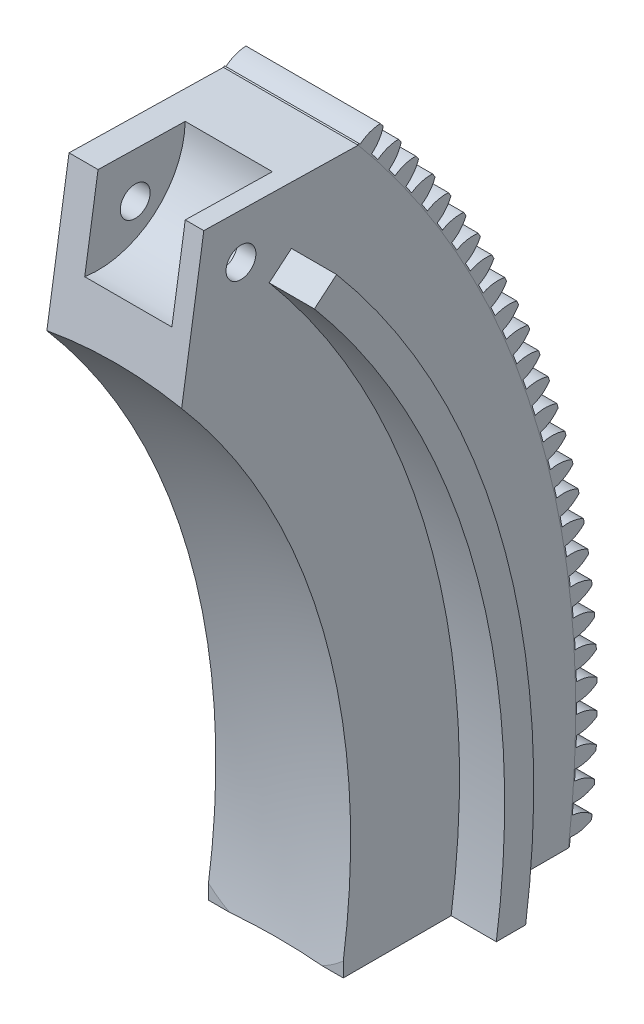
SolidWorks part; units mm, degrees
material "ABS"
ref_plane "Front Plane" through (0, 0, 0) normal (0, 0, 1) x (1, 0, 0)
ref_plane "Top Plane" through (0, 0, 0) normal (0, 1, 0) x (1, 0, 0)
ref_plane "Right Plane" through (0, 0, 0) normal (1, 0, 0) x (0, 0, -1)
ref_plane "Plane2" through (6.35, 0, 0) normal (1, 0, 0) x (0, 0, -1)
sketch "Sketch1" plane through (0, 0, 0) normal (1, 0, 0) x (0, 0, -1)
  line L0 (-1000, 0) -> (152.4, 0) construction
  line L1 (152.4, 0) -> (152.4, -25.4)
  line L2 (0, 0) -> (116.7452, 97.9608) construction
  line L4 (203.2, 0) -> (49000, 0) construction
  line L7 (152.4, -25.4) -> (203.2, -25.4) construction
  line L8 (203.2, 0) -> (203.2, -25.4) construction
  line L10 (-19.9245, -15.6845) -> (159.6649, 125.6875) construction
  line L61 (160.8976, 124.1056) -> (0, 0) construction
  line L62 (136.2027, 114.2876) -> (121.9167, 131.313) construction
  line L63 (116.7452, 97.9608) -> (121.9167, 131.313)
  line L64 (152.4, -25.4) -> (201.6062, -25.4)
  line L67 (121.9167, 131.313) -> (155.6602, 130.6144)
  line L68 (0, 0) -> (35966.99, 34732.9185) construction
  line L69 (159.6736, 125.6943) -> (159.6985, 125.714) construction
  arc A2 (152.4, 0) -> (116.7452, 97.9608) centre (0, 0) ccw
  circle A19 centre (0, 0) radius 203.2 construction
  arc A22 (155.6602, 130.6144) -> (203.2, 0) centre (0, 0) cw
  arc A23 (203.2, 0) -> (201.6062, -25.4) centre (0, 0) cw
  point P6 (159.6985, 125.714)
  point P7 (116.7452, 97.9608)
  dimension "D1" = 152.4
  dimension "D2" = 6.35
  dimension "D12" = 406.4
  dimension "D3" = 40
  dimension "D4" = 50.8
  dimension "D5" = 25.4
  dimension "D11" = 22.225
  dimension "D13" = 44
sketch "Sketch2" plane through (6.35, 0, 0) normal (1, 0, 0) x (0, 0, -1)
  line L0 (0, 0) -> (165.1, 0) construction
  line L1 (165.1, 0) -> (190.5, 0) construction
  line L2 (0, 0) -> (49240.3877, 8682.4089) construction
  circle A0 centre (165.1, 0) radius 3.2639
  circle A1 centre (190.5, 0) radius 3.2639
  arc A3 (165.1, 0) -> (162.5918, 28.6693) centre (0, 0) ccw construction
  circle A4 centre (162.5918, 28.6693) radius 3.2639
  arc A5 (190.5, 0) -> (187.6059, 33.08) centre (0, 0) ccw construction
  circle A6 centre (187.6059, 33.08) radius 3.2639
  dimension "D3" = 6.5278
  dimension "D4" = 6.5278
  dimension "D6" = 6.5278
  dimension "D7" = 6.5278
  dimension "D1" = 165.1
  dimension "D2" = 25.4
  dimension "D5" = 10
sketch "Sketch11" plane through (6.35, 0, 0) normal (1, 0, 0) x (0, 0, -1)
  line L0 (-785.502, -659.1144) -> (0, 0) construction
  line L2 (-1000, 0) -> (0, 0) construction
  line L4 (155.6602, 130.6144) -> (159.3372, 133.6998)
  line L5 (159.3372, 133.6998) -> (921.7047, 773.4021) construction
  line L6 (208, 0) -> (208, -25.4) construction
  line L7 (208, -25.4) -> (198.9391, -25.4) construction
  line L8 (201.6062, -25.4) -> (206.4433, -25.4)
  line L9 (203.2, 0) -> (208, 0) construction
  arc A0 (-230, 0) -> (-176.1902, -147.8412) centre (0, 0) ccw construction
  arc A1 (-208, 0) -> (-159.3372, -133.6998) centre (0, 0) ccw construction
  arc A2 (-205.6, 0) -> (-157.4987, -132.1571) centre (0, 0) ccw construction
  arc A3 (208, 0) -> (159.3372, 133.6998) centre (0, 0) ccw
  arc A4 (230, 0) -> (176.1902, 147.8412) centre (0, 0) ccw construction
  arc A5 (-205.6, 0) -> (-157.4987, -132.1571) centre (0, 0) ccw
  arc A6 (155.6602, 130.6144) -> (203.2, 0) centre (0, 0) cw
  arc A7 (208, 0) -> (206.4433, -25.4) centre (0, 0) cw
  arc A8 (203.2, 0) -> (201.6062, -25.4) centre (0, 0) cw
  dimension "D1" = 460
  dimension "D2" = 416
  dimension "D4" = 203.2
  dimension "D3" = 2.4
  dimension "D6" = 25.4
extrude "Boss-Extrude2" add sketch "Sketch11" against normal blind 6.35 contours A3 L4 region at (6.35, 130.8741, -158.5753)
sketch "Sketch12" plane through (6.35, 0, 0) normal (1, 0, 0) x (0, 0, -1)
  line L0 (0, 0) -> (208, 0) construction
  line L2 (205.994, 1.5708) -> (205.994, -1.5708) construction
  line L3 (0, 0) -> (203.4969, 1.1234) construction
  line L4 (201.6783, 0) -> (208.9831, 2.6587) construction
  line L5 (0, 0) -> (208.9757, 3.1872) construction
  line L6 (205.994, 1.5708) -> (205.9461, 4.712) construction
  circle A0 centre (0, 0) radius 206 construction
  arc A1 (206.4433, -25.4) -> (159.3372, 133.6998) centre (0, 0) ccw construction
  circle A2 centre (0, 0) radius 203.5 construction
  arc A3 (203.4969, 1.1234) -> (208.9694, 3.5771) centre (203.4559, 8.5441) ccw
  arc A4 (207.4358, -25.5221) -> (208.9694, -3.5771) centre (0, 0) cw construction
  arc A5 (203.4969, -1.1234) -> (208.9694, -3.5771) centre (203.4559, -8.5441) cw
  arc A6 (207.4358, -25.5221) -> (160.1033, 134.3426) centre (0, 0) ccw
  arc A7 (207.4358, -25.5221) -> (208.9694, 3.5771) centre (0, 0) ccw construction
  arc A8 (203.4969, 1.1234) -> (203.4969, -1.1234) centre (0, 0) cw
  arc A9 (206.4433, -25.4) -> (159.3372, 133.6998) centre (0, 0) ccw construction
  arc A10 (208.9694, 3.5771) -> (208.9694, -3.5771) centre (0, 0) cw
  point P9 (208.9694, -3.118)
  point P23 (208.9694, -3.525)
  dimension "D1" = 412
  dimension "D3" = 20
  dimension "D4" = 0.874
  dimension "D5" = 4.5
  dimension "D2" = 1
extrude "Boss-Extrude3" add sketch "Sketch1" along normal blind 29.464
extrude "Cut-Extrude4" cut sketch "Sketch12" against normal blind 6.35
pattern_circular "CirPattern3" count 206 every 1.748 about axis through (0, 0, 0) along (1, 0, 0) of "Cut-Extrude4"
sketch "Sketch15" plane through (6.35, 0, 0) normal (1, 0, 0) x (0, 0, -1)
  line L0 (0, 0) -> (130.0347, 121.2593) construction
  line L1 (-196961.5506, -34729.6355) -> (246201.9383, 43412.0444) construction
  circle A0 centre (130.0347, 121.2593) radius 3.2639
  dimension "D3" = 6.5278
  dimension "D1" = 177.8
  dimension "D2" = 33
extrude "Cut-Extrude7" cut sketch "Sketch15" against normal through all both and the other way through all
sketch "Sketch21" plane through (0, 0, 0) normal (0, 1, 0) x (1, 0, 0)
  line L0 (0, 0) -> (-11.1125, 0) construction
  line L1 (12.7, 0) -> (12.7, 152.4) construction
  line L2 (0, 0) -> (12.7, 0) construction
  line L3 (-11.1125, 0) -> (-11.1125, 38.1) construction
  line L4 (-11.1125, 38.1) -> (-127.8666, 38.1) construction
  line L5 (-11.1125, 38.1) -> (105.6416, 38.1) construction
  line L6 (107.5153, 38.1) -> (-49892.4847, 38.1) construction
  line L7 (-1000, 0) -> (49000, 0) construction
  line L8 (14.732, 38.1) -> (14.732, 152.4) construction
  line L9 (29.464, 152.4) -> (0, 152.4) construction
  line L10 (-76.1776, 38.1) -> (157.3306, 38.1) construction
  line L11 (29.464, 152.4) -> (0, 152.4) construction
  line L12 (0, 152.4) -> (14.732, 152.4) construction
  line L13 (14.732, 152.4) -> (14.732, 130.0627) construction
  line L15 (-76.1776, 38.1) -> (-102.108, 38.1)
  line L16 (105.6416, 38.1) -> (131.572, 38.1)
  line L17 (-76.1776, 38.1) -> (105.6416, 38.1)
  arc A0 (105.6416, 38.1) -> (-127.8666, 38.1) centre (-11.1125, 38.1) ccw construction
  arc A1 (-76.1776, 38.1) -> (157.3306, 38.1) centre (40.5765, 38.1) cw construction
  arc A2 (-102.108, 38.1) -> (131.572, 38.1) centre (14.732, 38.1) cw
  dimension "D3" = 12.7
  dimension "D5" = 116.84
  dimension "D1" = 11.1125
  dimension "D2" = 152.4
  dimension "D4" = 38.1
revolve "Cut-Revolve7" cut sketch "Sketch21" angle 360 about L7 reverse direction yes
sketch "Sketch22" plane through (6.35, 0, 0) normal (1, 0, 0) x (0, 0, -1)
  line L0 (0, 0) -> (130.0347, 121.2593)
  line L1 (0, 0) -> (177.8, 0)
  dimension "D1" = 177.8
sketch "Sketch23" plane through (0, 0, 0) normal (1, 0, 0) x (0, 0, -1)
  line L0 (0, 0) -> (152.4, 0) construction
  line L1 (0, 0) -> (116.7452, 97.9608) construction
  line L2 (152.4, 0) -> (171.45, 0) construction
  line L3 (116.7452, 97.9608) -> (136.2027, 114.2876) construction
  line L5 (136.2027, 114.2876) -> (141.0671, 118.3693)
  line L7 (175.9764, -25.4) -> (0, 0) construction
  line L8 (182.3899, -25.4) -> (175.9764, -25.4)
  line L9 (152.4, -25.4) -> (201.9086, -25.4) construction
  arc A0 (152.4, 0) -> (116.7452, 97.9608) centre (0, 0) ccw construction
  circle A2 centre (171.45, 0) radius 6.35 construction
  arc A3 (177.8, 0) -> (136.2027, 114.2876) centre (0, 0) ccw
  arc A4 (184.15, 0) -> (141.0671, 118.3693) centre (0, 0) ccw
  circle A5 centre (190.5, 0) radius 6.35 construction
  arc A6 (177.8, 0) -> (175.9764, -25.4) centre (0, 0) cw
  arc A7 (184.15, 0) -> (182.3899, -25.4) centre (0, 0) cw
  point P14 (0, 0)
  point P17 (0, 0)
  point P18 (0, 0)
  dimension "D4" = 6.35
  dimension "D5" = 12.7
  dimension "D6" = 12.7
  dimension "D1" = 152.4
  dimension "D2" = 40
  dimension "D3" = 19.05
extrude "Boss-Extrude4" add sketch "Sketch23" against normal blind 9.8742
ref_plane "Plane3" through (14.732, 0, 0) normal (1, 0, 0) x (0, 0, -1)
mirror "Mirror2" about plane through (14.732, 0, 0) normal (1, 0, 0) of "Boss-Extrude4"
sketch "Sketch24" plane through (0, -15.3774, -99.171) normal (0, 0.1532, 0.9882) x (1, 0, 0)
  line L0 (0, 148.4434) -> (6.35, 148.4434) construction
  line L1 (29.464, 148.4434) -> (0, 148.4434) construction
  line L3 (6.35, 148.4434) -> (25.4, 148.4434)
  line L4 (6.35, 148.4434) -> (6.35, 129.3934)
  line L5 (6.35, 129.3934) -> (25.4, 129.3934)
  line L6 (25.4, 148.4434) -> (25.4, 129.3934)
  dimension "D1" = 6.35
  dimension "D2" = 19.05
  dimension "D3" = 19.05
revolve "Cut-Revolve8" cut sketch "Sketch24" angle 360 about L0
sketch "Sketch27" plane through (6.35, 0, 0) normal (1, 0, 0) x (0, 0, -1)
  line L2 (155.89, 130.8073) -> (155.6602, 130.6144)
  line L3 (201.6062, -25.4) -> (201.9086, -25.4)
  line L4 (155.89, 130.8073) -> (155.6602, 130.6144)
  line L6 (201.6062, -25.4) -> (201.9086, -25.4)
  arc A95 (207.805, 9.0055) -> (207.7585, 10.0204) centre (0, 0) ccw
  arc A111 (203.368, 7.3287) -> (207.805, 9.0055) centre (203.1007, 14.7447) ccw
  arc A112 (203.368, 7.3287) -> (207.805, 9.0055) centre (203.1007, 14.7447) ccw
  arc A113 (207.7585, 10.0204) -> (203.1869, 11.2847) centre (203.5984, 3.8753) ccw
  arc A114 (207.7585, 10.0204) -> (203.1869, 11.2847) centre (203.5984, 3.8753) ccw
  arc A115 (203.1869, 11.2847) -> (203.0499, 13.5273) centre (0, 0) ccw
  arc A116 (203.1869, 11.2847) -> (203.0499, 13.5273) centre (0, 0) ccw
  arc A117 (203.0499, 13.5273) -> (207.4337, 15.3385) centre (202.5566, 20.9317) ccw
  arc A118 (203.0499, 13.5273) -> (207.4337, 15.3385) centre (202.5566, 20.9317) ccw
  arc A119 (207.4337, 15.3385) -> (207.3563, 16.3516) centre (0, 0) ccw
  arc A120 (207.4337, 15.3385) -> (207.3563, 16.3516) centre (0, 0) ccw
  arc A121 (207.3563, 16.3516) -> (202.7482, 17.4759) centre (203.3855, 10.0825) ccw
  arc A122 (207.3563, 16.3516) -> (202.7482, 17.4759) centre (203.3855, 10.0825) ccw
  arc A123 (202.7482, 17.4759) -> (202.5429, 19.7132) centre (0, 0) ccw
  arc A124 (202.7482, 17.4759) -> (202.5429, 19.7132) centre (0, 0) ccw
  arc A125 (202.5429, 19.7132) -> (206.8694, 21.6573) centre (201.8241, 27.0991) ccw
  arc A126 (202.5429, 19.7132) -> (206.8694, 21.6573) centre (201.8241, 27.0991) ccw
  arc A127 (206.8694, 21.6573) -> (206.7612, 22.6675) centre (0, 0) ccw
  arc A128 (206.8694, 21.6573) -> (206.7612, 22.6675) centre (0, 0) ccw
  arc A129 (206.7612, 22.6675) -> (202.121, 23.6508) centre (202.9834, 16.2802) ccw
  arc A130 (206.7612, 22.6675) -> (202.121, 23.6508) centre (202.9834, 16.2802) ccw
  arc A131 (202.121, 23.6508) -> (201.8476, 25.8808) centre (0, 0) ccw
  arc A132 (202.121, 23.6508) -> (201.8476, 25.8808) centre (0, 0) ccw
  arc A133 (201.8476, 25.8808) -> (206.1127, 27.956) centre (200.9038, 33.2414) ccw
  arc A134 (201.8476, 25.8808) -> (206.1127, 27.956) centre (200.9038, 33.2414) ccw
  arc A135 (206.1127, 27.956) -> (205.9737, 28.9624) centre (0, 0) ccw
  arc A136 (206.1127, 27.956) -> (205.9737, 28.9624) centre (0, 0) ccw
  arc A137 (205.9737, 28.9624) -> (201.3057, 29.8037) centre (202.3925, 22.4629) ccw
  arc A138 (205.9737, 28.9624) -> (201.3057, 29.8037) centre (202.3925, 22.4629) ccw
  arc A139 (201.3057, 29.8037) -> (200.9644, 32.0244) centre (0, 0) ccw
  arc A140 (201.3057, 29.8037) -> (200.9644, 32.0244) centre (0, 0) ccw
  arc A141 (200.9644, 32.0244) -> (205.1643, 34.2286) centre (199.7966, 39.3527) ccw
  arc A142 (200.9644, 32.0244) -> (205.1643, 34.2286) centre (199.7966, 39.3527) ccw
  arc A143 (205.1643, 34.2286) -> (204.9947, 35.2304) centre (0, 0) ccw
  arc A144 (205.1643, 34.2286) -> (204.9947, 35.2304) centre (0, 0) ccw
  arc A145 (204.9947, 35.2304) -> (200.3032, 35.9289) centre (201.6134, 28.6246) ccw
  arc A146 (204.9947, 35.2304) -> (200.3032, 35.9289) centre (201.6134, 28.6246) ccw
  arc A147 (200.3032, 35.9289) -> (199.8943, 38.1381) centre (0, 0) ccw
  arc A148 (200.3032, 35.9289) -> (199.8943, 38.1381) centre (0, 0) ccw
  arc A149 (199.8943, 38.1381) -> (204.0251, 40.4694) centre (198.5036, 45.4275) ccw
  arc A150 (199.8943, 38.1381) -> (204.0251, 40.4694) centre (198.5036, 45.4275) ccw
  arc A151 (204.0251, 40.4694) -> (203.825, 41.4655) centre (0, 0) ccw
  arc A152 (204.0251, 40.4694) -> (203.825, 41.4655) centre (0, 0) ccw
  arc A153 (203.825, 41.4655) -> (199.1143, 42.0207) centre (200.6467, 34.7598) ccw
  arc A154 (203.825, 41.4655) -> (199.1143, 42.0207) centre (200.6467, 34.7598) ccw
  arc A155 (199.1143, 42.0207) -> (198.6383, 44.2164) centre (0, 0) ccw
  arc A156 (199.1143, 42.0207) -> (198.6383, 44.2164) centre (0, 0) ccw
  arc A157 (198.6383, 44.2164) -> (202.696, 46.6726) centre (197.0259, 51.4599) ccw
  arc A158 (198.6383, 44.2164) -> (202.696, 46.6726) centre (197.0259, 51.4599) ccw
  arc A159 (202.696, 46.6726) -> (202.4656, 47.6621) centre (0, 0) ccw
  arc A160 (202.696, 46.6726) -> (202.4656, 47.6621) centre (0, 0) ccw
  arc A161 (202.4656, 47.6621) -> (197.7402, 48.0734) centre (199.4933, 40.8625) ccw
  arc A162 (202.4656, 47.6621) -> (197.7402, 48.0734) centre (199.4933, 40.8625) ccw
  arc A163 (197.7402, 48.0734) -> (197.1975, 50.2535) centre (0, 0) ccw
  arc A164 (197.7402, 48.0734) -> (197.1975, 50.2535) centre (0, 0) ccw
  arc A165 (197.1975, 50.2535) -> (201.1784, 52.8323) centre (195.3649, 57.4445) ccw
  arc A166 (197.1975, 50.2535) -> (201.1784, 52.8323) centre (195.3649, 57.4445) ccw
  arc A167 (201.1784, 52.8323) -> (200.9179, 53.8144) centre (0, 0) ccw
  arc A168 (201.1784, 52.8323) -> (200.9179, 53.8144) centre (0, 0) ccw
  arc A169 (200.9179, 53.8144) -> (196.1822, 54.0813) centre (198.1544, 46.9273) ccw
  arc A170 (200.9179, 53.8144) -> (196.1822, 54.0813) centre (198.1544, 46.9273) ccw
  arc A171 (196.1822, 54.0813) -> (195.5732, 56.2439) centre (0, 0) ccw
  arc A172 (196.1822, 54.0813) -> (195.5732, 56.2439) centre (0, 0) ccw
  arc A173 (195.5732, 56.2439) -> (199.4736, 58.9429) centre (193.5222, 63.3757) ccw
  arc A174 (195.5732, 56.2439) -> (199.4736, 58.9429) centre (193.5222, 63.3757) ccw
  arc A175 (199.4736, 58.9429) -> (199.1834, 59.9166) centre (0, 0) ccw
  arc A176 (199.4736, 58.9429) -> (199.1834, 59.9166) centre (0, 0) ccw
  arc A177 (199.1834, 59.9166) -> (194.4417, 60.039) centre (196.6311, 52.9484) ccw
  arc A178 (199.1834, 59.9166) -> (194.4417, 60.039) centre (196.6311, 52.9484) ccw
  arc A179 (194.4417, 60.039) -> (193.767, 62.182) centre (0, 0) ccw
  arc A180 (194.4417, 60.039) -> (193.767, 62.182) centre (0, 0) ccw
  arc A181 (193.767, 62.182) -> (197.5833, 64.9987) centre (191.4995, 69.2479) ccw
  arc A182 (201.6062, -25.4) -> (155.6602, 130.6144) centre (0, 0) ccw
  arc A183 (193.767, 62.182) -> (197.5833, 64.9987) centre (191.4995, 69.2479) ccw
  arc A184 (197.5833, 64.9987) -> (197.2635, 65.963) centre (0, 0) ccw
  arc A185 (197.5833, 64.9987) -> (197.2635, 65.963) centre (0, 0) ccw
  arc A186 (197.2635, 65.963) -> (192.5203, 65.9408) centre (194.9249, 58.9203) ccw
  arc A187 (197.2635, 65.963) -> (192.5203, 65.9408) centre (194.9249, 58.9203) ccw
  arc A189 (207.805, 9.0055) -> (207.7585, 10.0204) centre (0, 0) ccw
  arc A276 (201.6062, -25.4) -> (155.6602, 130.6144) centre (0, 0) ccw
  arc A282 (192.5203, 65.9408) -> (191.7806, 68.0622) centre (0, 0) ccw
  arc A283 (192.5203, 65.9408) -> (191.7806, 68.0622) centre (0, 0) ccw
  arc A284 (191.7806, 68.0622) -> (195.5092, 70.994) centre (189.2986, 75.0557) ccw
  arc A285 (191.7806, 68.0622) -> (195.5092, 70.994) centre (189.2986, 75.0557) ccw
  arc A286 (195.5092, 70.994) -> (195.1601, 71.9481) centre (0, 0) ccw
  arc A287 (195.5092, 70.994) -> (195.1601, 71.9481) centre (0, 0) ccw
  arc A288 (195.1601, 71.9481) -> (190.4198, 71.7812) centre (193.0374, 64.8374) ccw
  arc A289 (195.1601, 71.9481) -> (190.4198, 71.7812) centre (193.0374, 64.8374) ccw
  arc A290 (190.4198, 71.7812) -> (189.6157, 73.8791) centre (0, 0) ccw
  arc A291 (190.4198, 71.7812) -> (189.6157, 73.8791) centre (0, 0) ccw
  arc A292 (189.6157, 73.8791) -> (193.2532, 76.9233) centre (186.9217, 80.7937) ccw
  arc A293 (189.6157, 73.8791) -> (193.2532, 76.9233) centre (186.9217, 80.7937) ccw
  arc A294 (193.2532, 76.9233) -> (192.8752, 77.8663) centre (0, 0) ccw
  arc A295 (193.2532, 76.9233) -> (192.8752, 77.8663) centre (0, 0) ccw
  arc A296 (192.8752, 77.8663) -> (188.1422, 77.5549) centre (190.9703, 70.6941) ccw
  arc A297 (192.8752, 77.8663) -> (188.1422, 77.5549) centre (190.9703, 70.6941) ccw
  arc A298 (188.1422, 77.5549) -> (187.2745, 79.6273) centre (0, 0) ccw
  arc A299 (188.1422, 77.5549) -> (187.2745, 79.6273) centre (0, 0) ccw
  arc A300 (187.2745, 79.6273) -> (190.8175, 82.781) centre (184.3708, 86.4565) ccw
  arc A301 (187.2745, 79.6273) -> (190.8175, 82.781) centre (184.3708, 86.4565) ccw
  arc A302 (190.8175, 82.781) -> (190.4109, 83.712) centre (0, 0) ccw
  arc A303 (190.8175, 82.781) -> (190.4109, 83.712) centre (0, 0) ccw
  arc A304 (190.4109, 83.712) -> (185.6896, 83.2565) centre (188.7256, 76.4851) ccw
  arc A305 (190.4109, 83.712) -> (185.6896, 83.2565) centre (188.7256, 76.4851) ccw
  arc A306 (185.6896, 83.2565) -> (184.7591, 85.3014) centre (0, 0) ccw
  arc A307 (185.6896, 83.2565) -> (184.7591, 85.3014) centre (0, 0) ccw
  arc A308 (184.7591, 85.3014) -> (188.2042, 88.5617) centre (181.6485, 92.0389) ccw
  arc A309 (184.7591, 85.3014) -> (188.2042, 88.5617) centre (181.6485, 92.0389) ccw
  arc A310 (188.2042, 88.5617) -> (187.7694, 89.4799) centre (0, 0) ccw
  arc A311 (188.2042, 88.5617) -> (187.7694, 89.4799) centre (0, 0) ccw
  arc A312 (187.7694, 89.4799) -> (183.0642, 88.8806) centre (186.3053, 82.2049) ccw
  arc A313 (187.7694, 89.4799) -> (183.0642, 88.8806) centre (186.3053, 82.2049) ccw
  arc A314 (183.0642, 88.8806) -> (182.0718, 90.8962) centre (0, 0) ccw
  arc A315 (183.0642, 88.8806) -> (182.0718, 90.8962) centre (0, 0) ccw
  arc A316 (182.0718, 90.8962) -> (185.4159, 94.26) centre (178.7571, 97.5357) ccw
  arc A317 (182.0718, 90.8962) -> (185.4159, 94.26) centre (178.7571, 97.5357) ccw
  arc A318 (185.4159, 94.26) -> (184.9533, 95.1645) centre (0, 0) ccw
  arc A319 (185.4159, 94.26) -> (184.9533, 95.1645) centre (0, 0) ccw
  arc A320 (184.9533, 95.1645) -> (180.2685, 94.422) centre (183.7117, 87.8483) ccw
  arc A321 (184.9533, 95.1645) -> (180.2685, 94.422) centre (183.7117, 87.8483) ccw
  arc A322 (180.2685, 94.422) -> (179.2151, 96.4064) centre (0, 0) ccw
  arc A323 (180.2685, 94.422) -> (179.2151, 96.4064) centre (0, 0) ccw
  arc A324 (179.2151, 96.4064) -> (182.4551, 99.8706) centre (175.6995, 102.9417) ccw
  arc A325 (179.2151, 96.4064) -> (182.4551, 99.8706) centre (175.6995, 102.9417) ccw
  arc A326 (182.4551, 99.8706) -> (181.9651, 100.7606) centre (0, 0) ccw
  arc A327 (182.4551, 99.8706) -> (181.9651, 100.7606) centre (0, 0) ccw
  arc A328 (181.9651, 100.7606) -> (177.3052, 99.8756) centre (180.9472, 93.4099) ccw
  arc A329 (181.9651, 100.7606) -> (177.3052, 99.8756) centre (180.9472, 93.4099) ccw
  arc A330 (177.3052, 99.8756) -> (176.1917, 101.827) centre (0, 0) ccw
  arc A331 (177.3052, 99.8756) -> (176.1917, 101.827) centre (0, 0) ccw
  arc A332 (176.1917, 101.827) -> (179.3246, 105.3884) centre (172.4785, 108.252) ccw
  arc A333 (176.1917, 101.827) -> (179.3246, 105.3884) centre (172.4785, 108.252) ccw
  arc A334 (179.3246, 105.3884) -> (178.8076, 106.263) centre (0, 0) ccw
  arc A335 (179.3246, 105.3884) -> (178.8076, 106.263) centre (0, 0) ccw
  arc A336 (178.8076, 106.263) -> (174.1769, 105.2362) centre (178.0144, 98.8847) ccw
  arc A337 (178.8076, 106.263) -> (174.1769, 105.2362) centre (178.0144, 98.8847) ccw
  arc A338 (174.1769, 105.2362) -> (173.0044, 107.1528) centre (0, 0) ccw
  arc A339 (174.1769, 105.2362) -> (173.0044, 107.1528) centre (0, 0) ccw
  arc A340 (173.0044, 107.1528) -> (176.0272, 110.8081) centre (169.097, 113.4616) ccw
  arc A341 (173.0044, 107.1528) -> (176.0272, 110.8081) centre (169.097, 113.4616) ccw
  arc A342 (176.0272, 110.8081) -> (175.4839, 111.6665) centre (0, 0) ccw
  arc A343 (176.0272, 110.8081) -> (175.4839, 111.6665) centre (0, 0) ccw
  arc A344 (175.4839, 111.6665) -> (170.8866, 110.499) centre (174.916, 104.2675) ccw
  arc A345 (175.4839, 111.6665) -> (170.8866, 110.499) centre (174.916, 104.2675) ccw
  arc A346 (170.8866, 110.499) -> (169.6562, 112.3789) centre (0, 0) ccw
  arc A347 (170.8866, 110.499) -> (169.6562, 112.3789) centre (0, 0) ccw
  arc A348 (169.6562, 112.3789) -> (172.5661, 116.1247) centre (165.5582, 118.5656) ccw
  arc A349 (169.6562, 112.3789) -> (172.5661, 116.1247) centre (165.5582, 118.5656) ccw
  arc A350 (172.5661, 116.1247) -> (171.9968, 116.9662) centre (0, 0) ccw
  arc A351 (172.5661, 116.1247) -> (171.9968, 116.9662) centre (0, 0) ccw
  arc A352 (171.9968, 116.9662) -> (167.4373, 115.659) centre (171.6549, 109.5532) ccw
  arc A353 (171.9968, 116.9662) -> (167.4373, 115.659) centre (171.6549, 109.5532) ccw
  arc A354 (167.4373, 115.659) -> (166.1502, 117.5005) centre (0, 0) ccw
  arc A355 (167.4373, 115.659) -> (166.1502, 117.5005) centre (0, 0) ccw
  arc A356 (166.1502, 117.5005) -> (168.9445, 121.3333) centre (161.8654, 123.5593) ccw
  arc A357 (166.1502, 117.5005) -> (168.9445, 121.3333) centre (161.8654, 123.5593) ccw
  arc A358 (168.9445, 121.3333) -> (168.3498, 122.157) centre (0, 0) ccw
  arc A359 (168.9445, 121.3333) -> (168.3498, 122.157) centre (0, 0) ccw
  arc A360 (168.3498, 122.157) -> (163.8323, 120.7114) centre (168.2341, 114.7371) ccw
  arc A361 (168.3498, 122.157) -> (163.8323, 120.7114) centre (168.2341, 114.7371) ccw
  arc A362 (163.8323, 120.7114) -> (162.4896, 122.5128) centre (0, 0) ccw
  arc A363 (163.8323, 120.7114) -> (162.4896, 122.5128) centre (0, 0) ccw
  arc A364 (162.4896, 122.5128) -> (165.1657, 126.429) centre (158.022, 128.4382) ccw
  arc A365 (162.4896, 122.5128) -> (165.1657, 126.429) centre (158.022, 128.4382) ccw
  arc A366 (165.1657, 126.429) -> (164.5462, 127.2342) centre (0, 0) ccw
  arc A367 (165.1657, 126.429) -> (164.5462, 127.2342) centre (0, 0) ccw
  arc A368 (164.5462, 127.2342) -> (160.0748, 125.6515) centre (164.6568, 119.8142) ccw
  arc A369 (164.5462, 127.2342) -> (160.0748, 125.6515) centre (164.6568, 119.8142) ccw
  arc A370 (160.0748, 125.6515) -> (158.6778, 127.4111) centre (0, 0) ccw
  arc A371 (160.0748, 125.6515) -> (158.6778, 127.4111) centre (0, 0) ccw
  arc A372 (158.6778, 127.4111) -> (161.2333, 131.4071) centre (154.0317, 133.1975) ccw
  arc A373 (158.6778, 127.4111) -> (161.2333, 131.4071) centre (154.0317, 133.1975) ccw
  arc A374 (161.2333, 131.4071) -> (160.5895, 132.1931) centre (0, 0) ccw
  arc A375 (161.2333, 131.4071) -> (160.5895, 132.1931) centre (0, 0) ccw
  arc A376 (160.5895, 132.1931) -> (156.1685, 130.4747) centre (160.9264, 124.7799) ccw
  arc A377 (160.5895, 132.1931) -> (156.1685, 130.4747) centre (160.9264, 124.7799) ccw
  arc A378 (156.1685, 130.4747) -> (155.89, 130.8073) centre (0, 0) ccw
  arc A379 (156.1685, 130.4747) -> (155.89, 130.8073) centre (0, 0) ccw
  arc A380 (203.4969, -1.1234) -> (203.4969, 1.1234) centre (0, 0) ccw
  arc A381 (203.4969, -1.1234) -> (203.4969, 1.1234) centre (0, 0) ccw
  arc A382 (203.4969, 1.1234) -> (207.9829, 2.664) centre (203.4559, 8.5441) ccw
  arc A383 (203.4969, 1.1234) -> (207.9829, 2.664) centre (203.4559, 8.5441) ccw
  arc A384 (207.9829, 2.664) -> (207.9675, 3.6799) centre (0, 0) ccw
  arc A385 (207.9829, 2.664) -> (207.9675, 3.6799) centre (0, 0) ccw
  arc A386 (207.9675, 3.6799) -> (203.4365, 5.083) centre (203.6219, -2.3355) ccw
  arc A387 (207.9675, 3.6799) -> (203.4365, 5.083) centre (203.6219, -2.3355) ccw
  arc A388 (203.4365, 5.083) -> (203.368, 7.3287) centre (0, 0) ccw
  arc A389 (203.4365, 5.083) -> (203.368, 7.3287) centre (0, 0) ccw
  arc A390 (201.9086, -25.4) -> (202.121, -23.6508) centre (0, 0) ccw
  arc A391 (201.9086, -25.4) -> (202.121, -23.6508) centre (0, 0) ccw
  arc A392 (202.121, -23.6508) -> (206.7612, -22.6675) centre (202.9834, -16.2802) ccw
  arc A393 (202.121, -23.6508) -> (206.7612, -22.6675) centre (202.9834, -16.2802) ccw
  arc A394 (206.7612, -22.6675) -> (206.8694, -21.6573) centre (0, 0) ccw
  arc A395 (206.7612, -22.6675) -> (206.8694, -21.6573) centre (0, 0) ccw
  arc A396 (206.8694, -21.6573) -> (202.5429, -19.7132) centre (201.8241, -27.0991) ccw
  arc A397 (206.8694, -21.6573) -> (202.5429, -19.7132) centre (201.8241, -27.0991) ccw
  arc A398 (202.5429, -19.7132) -> (202.7482, -17.4759) centre (0, 0) ccw
  arc A399 (202.5429, -19.7132) -> (202.7482, -17.4759) centre (0, 0) ccw
  arc A400 (202.7482, -17.4759) -> (207.3563, -16.3516) centre (203.3855, -10.0825) ccw
  arc A401 (202.7482, -17.4759) -> (207.3563, -16.3516) centre (203.3855, -10.0825) ccw
  arc A402 (207.3563, -16.3516) -> (207.4337, -15.3385) centre (0, 0) ccw
  arc A403 (207.3563, -16.3516) -> (207.4337, -15.3385) centre (0, 0) ccw
  arc A404 (207.4337, -15.3385) -> (203.0499, -13.5273) centre (202.5566, -20.9317) ccw
  arc A405 (207.4337, -15.3385) -> (203.0499, -13.5273) centre (202.5566, -20.9317) ccw
  arc A406 (203.0499, -13.5273) -> (203.1869, -11.2847) centre (0, 0) ccw
  arc A407 (203.0499, -13.5273) -> (203.1869, -11.2847) centre (0, 0) ccw
  arc A408 (203.1869, -11.2847) -> (207.7585, -10.0204) centre (203.5984, -3.8753) ccw
  arc A409 (203.1869, -11.2847) -> (207.7585, -10.0204) centre (203.5984, -3.8753) ccw
  arc A410 (207.7585, -10.0204) -> (207.805, -9.0055) centre (0, 0) ccw
  arc A411 (207.7585, -10.0204) -> (207.805, -9.0055) centre (0, 0) ccw
  arc A412 (207.805, -9.0055) -> (203.368, -7.3287) centre (203.1007, -14.7447) ccw
  arc A413 (207.805, -9.0055) -> (203.368, -7.3287) centre (203.1007, -14.7447) ccw
  arc A414 (203.368, -7.3287) -> (203.4365, -5.083) centre (0, 0) ccw
  arc A415 (203.368, -7.3287) -> (203.4365, -5.083) centre (0, 0) ccw
  arc A416 (203.4365, -5.083) -> (207.9675, -3.6799) centre (203.6219, 2.3355) ccw
  arc A417 (203.4365, -5.083) -> (207.9675, -3.6799) centre (203.6219, 2.3355) ccw
  arc A418 (207.9675, -3.6799) -> (207.9829, -2.664) centre (0, 0) ccw
  arc A419 (207.9675, -3.6799) -> (207.9829, -2.664) centre (0, 0) ccw
  arc A420 (207.9829, -2.664) -> (203.4969, -1.1234) centre (203.4559, -8.5441) ccw
  arc A421 (207.9829, -2.664) -> (203.4969, -1.1234) centre (203.4559, -8.5441) ccw
  dimension "D1" = 0
extrude "Boss-Extrude6" add sketch "Sketch27" along normal blind 23.0187
equation "\"Module\"= 2mm"
equation "\"Number of Teeth\"= 206"
equation "\"D1@Sketch12\"=\"Module\" * \"Number of Teeth\""
equation "\"D4@Sketch12\"=180 / \"Number of Teeth\""
equation "\"D2\"= 360 / \"Number of Teeth\""
equation "\"D2@Sketch11\"=( \"Number of Teeth\" + 2) * \"Module\""
equation "\"D2@CirPattern3\"= 360 / \"Number of Teeth\""
equation "\"D5@Sketch12\"= 2.25 * \"Module\""
equation "\"D1@Sketch26\"= \"Module\" * \"Number of Teeth\""
equation "\"D1@CirPattern3\"=\"Number of Teeth\""
